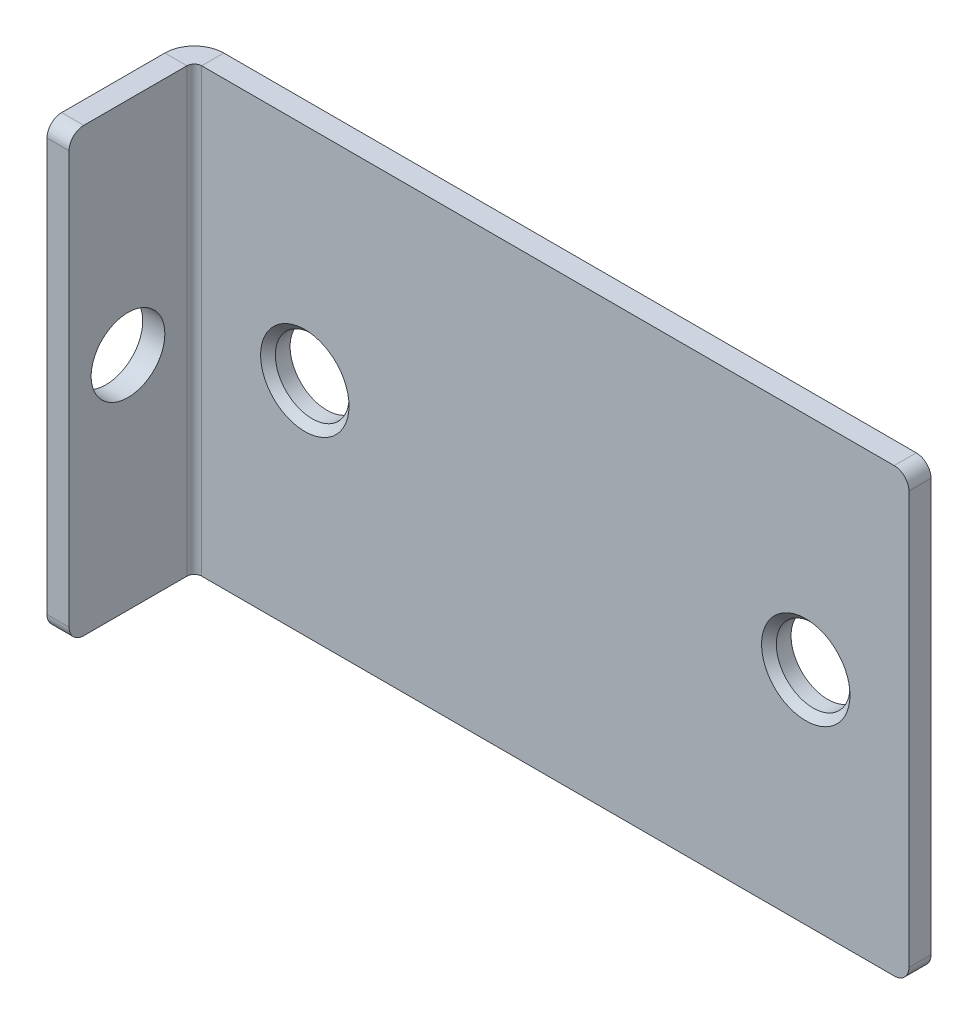
SolidWorks part; units mm, degrees
note: The reader was unsure of these and kept them because the rebuilt part matched: flange length of "Edge-Flange1".
ref_plane "Front Plane" through (0, 0, 0) normal (0, 0, 1) x (1, 0, 0)
ref_plane "Top Plane" through (0, 0, 0) normal (0, 1, 0) x (1, 0, 0)
ref_plane "Right Plane" through (0, 0, 0) normal (1, 0, 0) x (0, 0, -1)
sketch "Sketch1" plane through (0, 0, 0) normal (0, 0, 1) x (1, 0, 0)
  line L0 (0, -7.907) -> (0, 12.093)
  line L1 (0, 12.093) -> (95, 12.093)
  line L2 (95, 12.093) -> (95, -7.907)
  line L3 (95, -7.907) -> (0, -7.907)
  dimension "D1" = 20
  dimension "D2" = 95
sketch "Sketch2" plane through (0, 0, 0) normal (0, 0, 1) x (1, 0, 0)
  line L0 (0, -7.907) -> (0, 12.093) construction
  line L9 (0, 3.593) -> (5, 3.593)
  line L10 (0, 3.593) -> (0, 0.593)
  line L11 (0, 0.593) -> (5, 0.593)
  line L12 (5, 3.593) -> (5, 0.593)
  point P6 (0, 2.093)
  point P7 (0, 2.093)
  dimension "D1" = 3
  dimension "D2" = 5
base flange "Base-Flange1" sketch "Sketch2" thickness 0.15 reverse thickness direction no parameters "D1"=0.5
edge flange "Edge-Flange1" sketch "Sketch13" flange angle 90 flange length 1 flange position material inside bend radius 0.05 thickness 0.15 relief rectangular parameters "D6"=10
sketch "Sketch13" plane through (0, 0, 0) normal (-1, 0, 0) x (0, -1, 0)
  line L2 (-3.593, 0) -> (-3.593, 0.85)
  line L3 (-3.593, 0.85) -> (-0.593, 0.85)
  line L4 (-0.593, 0.85) -> (-0.593, 0)
  line L7 (-3.593, 0) -> (-0.593, 0) construction
  line L8 (-3.593, 0) -> (-0.593, 0)
bend "EdgeBend1" bend radius 0.05 bend angle 90 parameters "D5"=1
sketch "Sketch14" plane through (0.15, 0, 0) normal (1, 0, 0) x (0, 0, -1)
  line L0 (-0.85, 3.593) -> (-0.05, 3.593) construction
  line L1 (-0.85, 0.593) -> (-0.85, 3.593) construction
  circle A0 centre (-0.45, 2.093) radius 0.25
  point P7 (-0.85, 2.093)
  point P8 (-0.45, 3.593)
  dimension "D1" = 0.5
extrude "Cut-Extrude1" cut sketch "Sketch14" against normal through all normal cut yes
hole_wizard "CSK for M2 Flat Head Machine Screw1" positions "Sketch15" profile "Sketch17" countersink size "M2" standard "ANSI Metric" end condition through all
sketch "Sketch15" plane through (0, 0, 0) normal (0, 0, 1) x (1, 0, 0)
  line L0 (0.2, 3.593) -> (0.2, 0.593) construction
  line L2 (0.2, 2.093) -> (5, 2.093) construction
  line L3 (5, 0.593) -> (5, 3.593) construction
  point P0 (0.9, 2.093)
  point P2 (4.3, 2.093)
  point P14 (0.2, 2.093)
  dimension "D1" = 0.7
  dimension "D2" = 0.7
sketch "Sketch17" plane through (0.9, 2.093, 0) normal (1, 0, 0) x (0, -1, 0)
  line L0 (0, 0) -> (0, 0.15)
  line L1 (0, 0.15) -> (0.25, 0.15)
  line L2 (0.25, 0.15) -> (0.25, 0.05)
  line L3 (0.25, 0.05) -> (0.3, 0)
  line L5 (0.3, 0) -> (0, 0)
  line L6 (-0.25, 0.05) -> (-0.3, 0) construction
  line L11 (0, -6.35) -> (0, 107.95) construction
  dimension "Thru Hole Dia." = 0.5
  dimension "Thru Hole Depth" = 0.15
  dimension "Near C'Sink Dia." = 0.6
  dimension "Near C'Sink Angle" = 90
fillet "Fillet1" radius 0.1 4 edges at (0.075, 3.593, 0.85) (0.075, 0.593, 0.85) (5, 3.593, -0.075) (5, 0.593, -0.075)
sketch "Bend-Lines1" [suppressed] plane through (0, 0, 0) normal (0, 1, 0) x (1, 0, 0)
sketch "Bounding-Box1" [suppressed] plane through (0, 0, 0) normal (0, 1, 0) x (1, 0, 0)
sheet metal parameters "Sheet-Metal1" thickness 0.15 parameters "D1"=0.5
flat pattern "Flat-Pattern1" [suppressed]
sketch "Bend-Lines2" plane through (0, 0, 0) normal (0, 1, 0) x (1, 0, 0)
sketch3d "Bounding-Box2" [suppressed]
  line L0 (0, 0.593, 0) -> (-4, 0.593, 0) construction
  line L1 (0, 3.593, 0) -> (-4, 3.593, 0) construction
  line L2 (0, 0.593, 0) -> (0, 3.593, 0) construction
  line L3 (-4, 0.593, 0) -> (-4, 3.593, 0) construction
sheet metal parameters "Sheet-Metal2" thickness 0.15 parameters "D1"=0.5
flat pattern "Flat-Pattern1"
sketch "Bend-Lines2" plane through (0, 0, 0) normal (0, 0, 1) x (1, 0, 0)
  line L0 (0.1018, 3.593) -> (0.1018, 0.593) construction
  line L1 (0.1018, 3.593) -> (0.1018, 0.593) construction
sketch3d "Bounding-Box2" [suppressed]
  line L0 (-0.7963, 0.593, 0) -> (4, 0.593, 0) construction
  line L1 (-0.7963, 3.593, 0) -> (4, 3.593, 0) construction
  line L2 (-0.7963, 0.593, 0) -> (-0.7963, 3.593, 0) construction
  line L3 (4, 0.593, 0) -> (4, 3.593, 0) construction
bend of the flat pattern "Flatten-<EdgeBend1>1"
sheet metal parameters "Sheet-Metal3" thickness 0.15 parameters "D1"=0.5
flat pattern "Flat-Pattern1"
sketch "Bend-Lines2" plane through (0, 0, 0) normal (0, 0, 1) x (1, 0, 0)
  line L0 (0.1018, 2.843) -> (0.1018, 1.343) construction
  line L1 (0.1018, 2.843) -> (0.1018, 1.343) construction
sketch3d "Bounding-Box2" [suppressed]
  line L0 (-0.7963, 1.343, 0) -> (2, 1.343, 0) construction
  line L1 (-0.7963, 2.843, 0) -> (2, 2.843, 0) construction
  line L2 (-0.7963, 1.343, 0) -> (-0.7963, 2.843, 0) construction
  line L3 (2, 1.343, 0) -> (2, 2.843, 0) construction
bend of the flat pattern "Flatten-<EdgeBend1>1"
sheet metal parameters "Sheet-Metal4" thickness 0.15 parameters "D1"=0.5
flat pattern "Flat-Pattern1"
sketch "Bend-Lines2" plane through (0, 0, 0) normal (0, 0, 1) x (1, 0, 0)
  line L0 (0.1018, 3.593) -> (0.1018, 0.593) construction
  line L1 (0.1018, 3.593) -> (0.1018, 0.593) construction
sketch3d "Bounding-Box2" [suppressed]
  line L0 (-0.7963, 0.593, 0) -> (5, 0.593, 0) construction
  line L1 (-0.7963, 3.593, 0) -> (5, 3.593, 0) construction
  line L2 (-0.7963, 0.593, 0) -> (-0.7963, 3.593, 0) construction
  line L3 (5, 0.593, 0) -> (5, 3.593, 0) construction
bend of the flat pattern "Flatten-<EdgeBend1>1"
